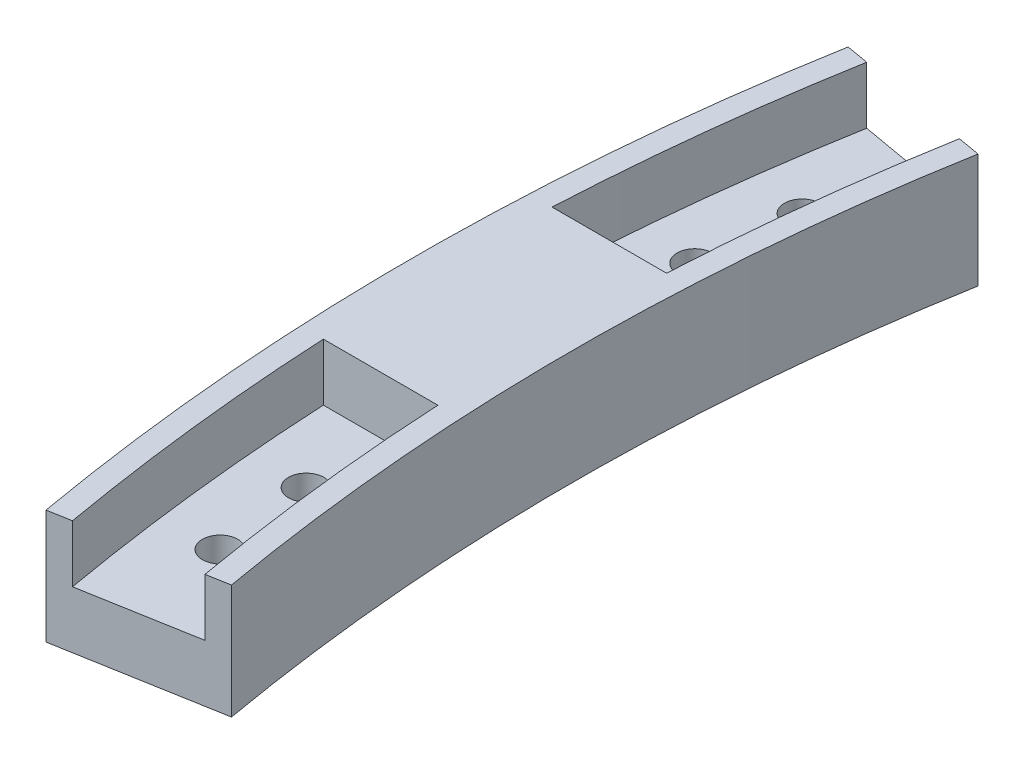
SolidWorks part; units mm, degrees
ref_plane "Front Plane" through (0, 0, 0) normal (0, 0, 1) x (1, 0, 0)
ref_plane "Top Plane" through (0, 0, 0) normal (0, 1, 0) x (1, 0, 0)
ref_plane "Right Plane" through (0, 0, 0) normal (1, 0, 0) x (0, 0, -1)
sketch "Sketch1" plane through (0, 0, 0) normal (0, 1, 0) x (1, 0, 0)
  line L0 (0, 0) -> (-196.9616, -34.7296) construction
  line L1 (0, 0) -> (-196.9616, 34.7296) construction
  line L2 (0, 0) -> (-195, 0) construction
  line L3 (-196.9616, 34.7296) -> (-187.1135, 32.9932)
  line L4 (-187.1135, -32.9932) -> (-196.9616, -34.7296)
  line L5 (0, 0) -> (-198.9312, -35.0769) construction
  line L6 (0, 0) -> (-198.9312, 35.0769) construction
  line L7 (-198.9312, 35.0769) -> (-185.1439, 32.6459)
  line L8 (-198.9312, -35.0769) -> (-185.1439, -32.6459)
  arc A0 (-196.9616, 34.7296) -> (-196.9616, -34.7296) centre (0, 0) ccw
  arc A1 (-187.1135, 32.9932) -> (-187.1135, -32.9932) centre (0, 0) ccw
  arc A2 (-192.0375, -33.8614) -> (-192.0375, 33.8614) centre (0, 0) cw construction
  arc A4 (-185.1439, 32.6459) -> (-185.1439, -32.6459) centre (0, 0) ccw
  arc A5 (-198.9312, 35.0769) -> (-198.9312, -35.0769) centre (0, 0) ccw
  dimension "D1" = 200
  dimension "D2" = 190
  dimension "D3" = 5
  dimension "D5" = 188
  dimension "D6" = 202
  dimension "D4" = 20
extrude "Boss-Extrude1" add sketch "Sketch1" along normal blind 10 contours A1 L3 A0 L4 | L7 A5 L8 A0 | A4 L7 A1 L8 region at (-200.7033, 0, 0) region at (-194.054, 0, 0) region at (-188.0437, 0, 0)
ref_plane "Plane1" through (-195, 0, 0) normal (1, 0, 0) x (0, 0, -1)
sketch "Sketch15" plane through (0, 10, 0) normal (0, 1, 0) x (1, 0, 0)
  line L0 (-187.1135, -32.9932) -> (-196.9616, -34.7296) construction
  line L1 (-185, 10) -> (-205, 10)
  line L2 (-185, 10) -> (-185, -10)
  line L3 (-185, -10) -> (-205, -10)
  line L4 (-205, 10) -> (-205, -10)
  line L5 (-185, 10) -> (-205, -10) construction
  line L6 (-185, -10) -> (-205, 10) construction
  line L7 (-196.9616, 34.7296) -> (-187.1135, 32.9932) construction
  line L8 (-187.1135, -32.9932) -> (-196.9616, -34.7296)
  line L9 (-196.9616, 34.7296) -> (-187.1135, 32.9932)
  arc A2 (-187.1135, 32.9932) -> (-187.1135, -32.9932) centre (0, 0) ccw construction
  arc A3 (-196.9616, 34.7296) -> (-196.9616, -34.7296) centre (0, 0) ccw construction
  arc A4 (-187.1135, 32.9932) -> (-187.1135, -32.9932) centre (0, 0) ccw
  arc A5 (-196.9616, 34.7296) -> (-196.9616, -34.7296) centre (0, 0) ccw
  point P0 (-195, 0)
  point P6 (0, 0)
  point P7 (-183.6647, 10)
  point P11 (-183.3534, 10)
  line M5 (-198.9312, -35.0769) -> (-185.1439, -32.6459)
  line M7 (-185.1439, 32.6459) -> (-198.9312, 35.0769)
  dimension "D1" = 20
  dimension "D2" = 20
extrude "Cut-Extrude1" cut sketch "Sketch15" against normal blind 5 contours A5 L1 A4 M7 | L3 A5 A4 M5 region at (-193.6958, 10, -21.9638) region at (-193.6958, 10, 21.9638)
ref_plane "Plane2" through (-195, 0, 0) normal (-1, 0, 0) x (0, 0, 1)
sketch "Sketch12" plane through (0, 0, 0) normal (0, 1, 0) x (1, 0, 0)
  line L0 (0, 0) -> (-194.258, -16.9954) construction
  line L1 (0, 0) -> (-193.3317, -25.4526) construction
  line L2 (0, 0) -> (-195, 0) construction
  line L3 (0, 0) -> (-195, 0) construction
  line L4 (0, 0) -> (-194.258, 16.9954) construction
  line L5 (0, 0) -> (-193.3317, 25.4526) construction
  arc A0 (-192.0375, 33.8614) -> (-192.0375, -33.8614) centre (0, 0) ccw construction
  point P11 (0, 0)
  dimension "D1" = 10
  dimension "D2" = 15
hole_wizard "Ø3.1 (3.1) Diameter Hole2" positions "Sketch18" profile "Sketch17" hole size "Ø3.1" standard "ISO" end condition through all
sketch "Sketch18" plane through (0, 0, 0) normal (0, -1, 0) x (-1, 0, 0)
  point P0 (193.3317, -25.4526)
  point P3 (194.258, -16.9954)
  point P6 (194.258, 16.9954)
  point P9 (193.3317, 25.4526)
sketch "Sketch17" plane through (-193.3317, 0, 25.4526) normal (1, 0, 0) x (0, 0, -1)
  line L0 (0, 0) -> (0, 10)
  line L1 (0, 10) -> (1.55, 10)
  line L2 (1.55, 10) -> (1.55, 0)
  line L5 (1.55, 0) -> (0, 0)
  line L11 (0, -6.35) -> (0, 107.95) construction
  dimension "Thru Hole Dia." = 3.1
  dimension "Thru Hole Depth" = 10
